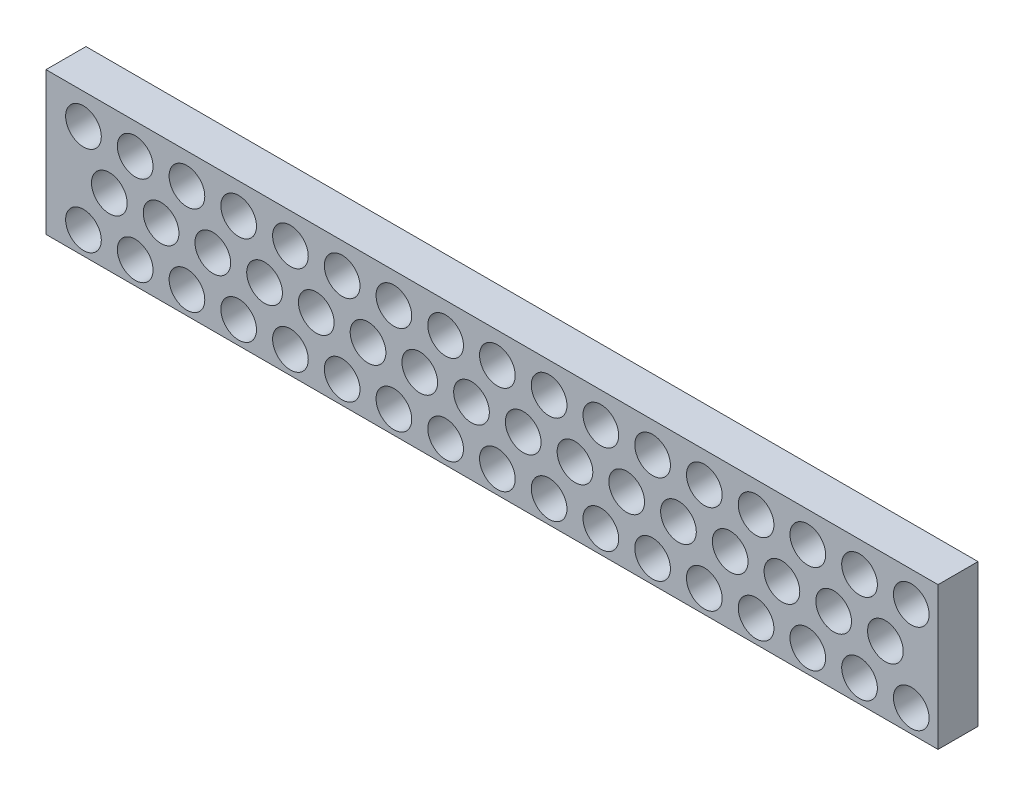
SolidWorks part; units mm, degrees
ref_plane "Front Plane" through (0, 0, 0) normal (0, 0, 1) x (1, 0, 0)
ref_plane "Top Plane" through (0, 0, 0) normal (0, 1, 0) x (1, 0, 0)
ref_plane "Right Plane" through (0, 0, 0) normal (1, 0, 0) x (0, 0, -1)
sketch "Sketch1" plane through (0, 0, 0) normal (0, 0, 1) x (1, 0, 0)
  line L0 (0, 0) -> (18.415, 0) construction
  line L1 (18.415, 0) -> (18.415, 31.8948) construction
  line L2 (18.415, 31.8948) -> (31.115, 31.8948) construction
  line L3 (37.465, -48.0416) -> (-597.535, -48.0416)
  line L4 (37.465, -48.0416) -> (37.465, 53.5584)
  line L5 (37.465, 53.5584) -> (-597.535, 53.5584)
  line L6 (-597.535, -48.0416) -> (-597.535, 53.5584)
  line L7 (18.415, 31.8948) -> (18.415, 44.5948) construction
  circle A0 centre (0, 0) radius 12.7
  circle A1 centre (18.415, 31.8948) radius 12.7
  circle A2 centre (18.415, -31.8948) radius 12.7
  dimension "D1" = 25.4
  dimension "D4" = 25.4
  dimension "D2" = 18.415
  dimension "D3" = 31.8948
  dimension "D5" = 6.35
  dimension "D6" = 635
  dimension "D7" = 8.9637
  dimension "D8" = 101.6
extrude "Boss-Extrude1" add sketch "Sketch1" against normal blind 28.448 contours L5 L6 L3 L4
extrude "Cut-Extrude1" cut sketch "Sketch1<3>" against normal through all both and the other way through all contours A1 | A0 | A2
sketch "Sketch1<3>" plane through (0, 0, 0) normal (0, 0, 1) x (1, 0, 0) same geometry as "Sketch1"
pattern_linear "LPattern1" count 16 spacing 36.83 along (-1, 0, 0) of "Cut-Extrude1"
sketch "Sketch3" plane through (0, 0, 0) normal (0, 0, 1) x (1, 0, 0)
  line L0 (18.415, -31.8948) -> (37.465, -31.8948) construction
  line L1 (-534.035, 31.8948) -> (-570.865, 31.8948) construction
  line L2 (37.465, -48.0416) -> (37.465, 53.5584) construction
  line L3 (-534.035, -31.8948) -> (-570.865, -31.8948) construction
  line L4 (0, 0) -> (37.465, 0) construction
  line L5 (37.465, 0) -> (-601.98, 0) construction
  circle A0 centre (-570.865, 31.8948) radius 12.7
  circle A1 centre (-570.865, -31.8948) radius 12.7
  dimension "D4" = 25.4
  dimension "D5" = 25.4
  dimension "D1" = 36.83
  dimension "D2" = 639.445
  dimension "D3" = 36.83
extrude "Cut-Extrude2" cut sketch "Sketch3" against normal through all both contours A0 | A1
